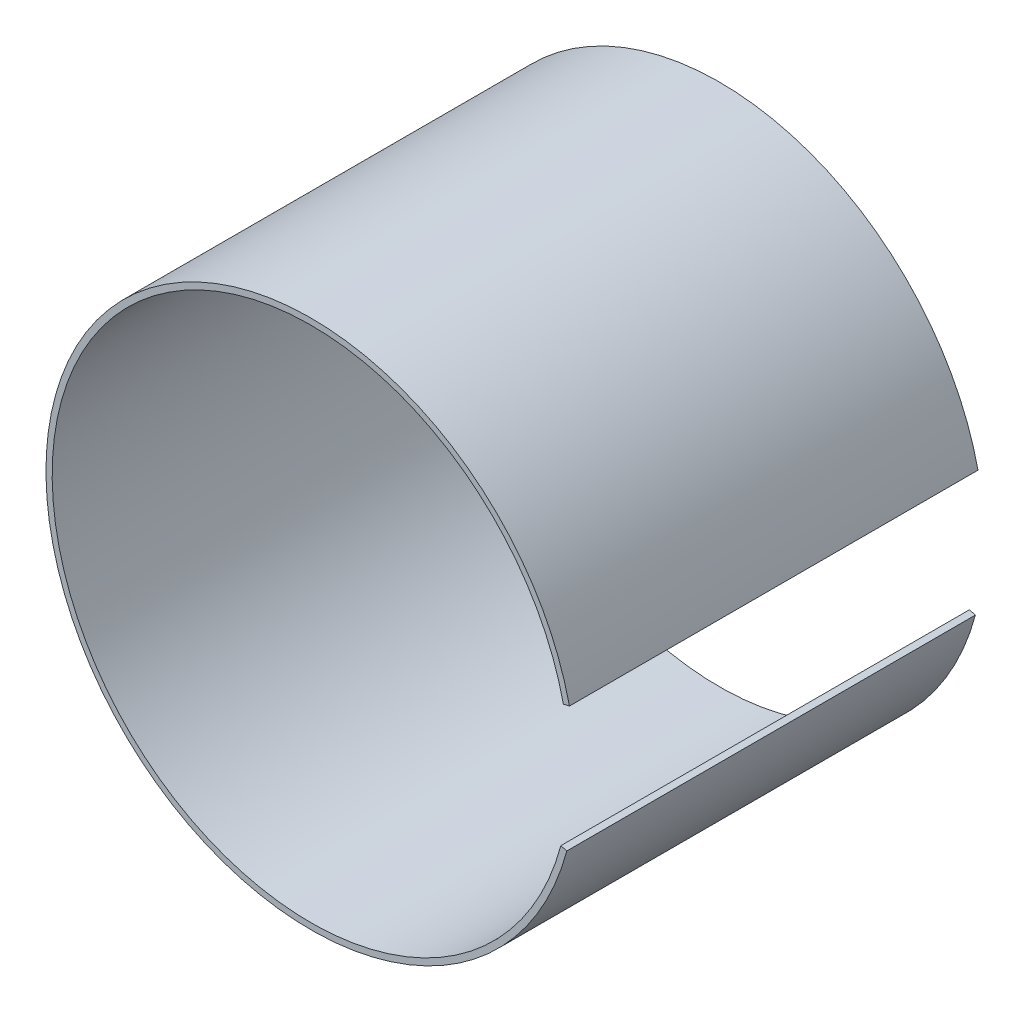
SolidWorks part; units mm, degrees
ref_plane "Front Plane" through (0, 0, 0) normal (0, 0, 1) x (1, 0, 0)
ref_plane "Top Plane" through (0, 0, 0) normal (0, 1, 0) x (1, 0, 0)
ref_plane "Right Plane" through (0, 0, 0) normal (1, 0, 0) x (0, 0, -1)
sketch "Sketch1" plane through (0, 0, 0) normal (0, 0, 1) x (1, 0, 0)
  line L0 (0, -55) -> (0, 55) construction
  line L1 (55, 0) -> (-55, 0) construction
  arc A0 (20.3911, 4.5842) -> (20.1861, -5.4158) centre (0, 0) ccw
  dimension "D1" = 10
  dimension "D2" = 20.9
extrude "Extrude-Thin1" add sketch "Sketch1" along normal blind 33 thin thin type one direction wall 0.5
